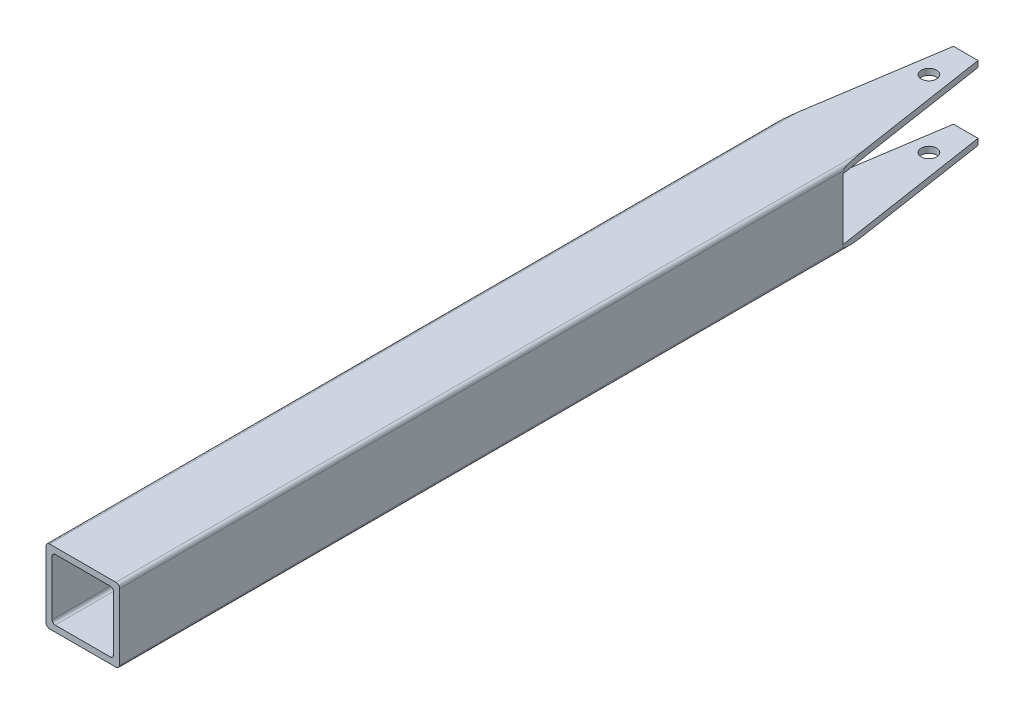
SolidWorks part; units mm, degrees
ref_plane "Front" through (0, 0, 0) normal (0, 0, 1) x (1, 0, 0)
ref_plane "Top" through (0, 0, 0) normal (0, 1, 0) x (1, 0, 0)
ref_plane "Right" through (0, 0, 0) normal (1, 0, 0) x (0, 0, -1)
sketch "Sketch1" plane through (0, 0, 0) normal (0, 0, 1) x (1, 0, 0)
  line L0 (-31.75, 0) -> (-38.1, 0) construction
  line L1 (34.29, -38.1) -> (-34.29, -38.1)
  line L2 (38.1, -34.29) -> (38.1, 34.29)
  line L3 (34.29, 38.1) -> (-34.29, 38.1)
  line L4 (-38.1, -34.29) -> (-38.1, 34.29)
  line L5 (38.1, -38.1) -> (-38.1, 38.1) construction
  line L6 (38.1, 38.1) -> (-38.1, -38.1) construction
  line L7 (28.575, 31.75) -> (-28.575, 31.75)
  line L8 (31.75, 28.575) -> (31.75, -28.575)
  line L9 (28.575, -31.75) -> (-28.575, -31.75)
  line L10 (-31.75, 28.575) -> (-31.75, -28.575)
  line L11 (31.75, 31.75) -> (-31.75, -31.75) construction
  line L12 (31.75, -31.75) -> (-31.75, 31.75) construction
  line L13 (0, -31.75) -> (0, -38.1) construction
  line L14 (31.75, -28.575) -> (31.75, -38.1) construction
  line L16 (31.75, -38.1) -> (38.1, -38.1) construction
  arc A0 (-28.575, -31.75) -> (-31.75, -28.575) centre (-28.575, -28.575) cw
  arc A1 (31.75, -28.575) -> (28.575, -31.75) centre (28.575, -28.575) cw
  arc A2 (28.575, 31.75) -> (31.75, 28.575) centre (28.575, 28.575) cw
  arc A3 (-28.575, 31.75) -> (-31.75, 28.575) centre (-28.575, 28.575) ccw
  arc A4 (34.29, -38.1) -> (38.1, -34.29) centre (34.29, -34.29) ccw
  arc A5 (38.1, 34.29) -> (34.29, 38.1) centre (34.29, 34.29) ccw
  arc A6 (-34.29, 38.1) -> (-38.1, 34.29) centre (-34.29, 34.29) ccw
  arc A7 (-34.29, -38.1) -> (-38.1, -34.29) centre (-34.29, -34.29) cw
  point P0 (0, 0)
  point P6 (0, 0)
  dimension "D2" = 3.175
  dimension "D3" = 3.81
sketch "Sketch2" plane through (0, 0, 0) normal (1, 0, 0) x (0, 0, -1)
  line L0 (-457.2, 0) -> (457.2, 0) construction
  dimension "Length" = 914.4
ref_plane "Plane1" through (38.1, 0, 0) normal (1, 0, 0) x (0, 0, -1)
sketch "Sketch5" plane through (38.1, 0, 0) normal (1, 0, 0) x (0, 0, -1)
  line L0 (-457.2, 38.1) -> (-457.2, -38.1) construction
  line L1 (457.2, 38.1) -> (457.2, -38.1) construction
sketch "Sketch4" plane through (0, 0, 0) normal (0, 0, 1) x (1, 0, 0)
  line L0 (38.1, -34.29) -> (38.1, 34.29) construction
  line L1 (34.29, 38.1) -> (-34.29, 38.1) construction
  line L2 (-38.1, -34.29) -> (-38.1, 34.29) construction
  line L3 (34.29, -38.1) -> (-34.29, -38.1) construction
  line L4 (31.75, 28.575) -> (31.75, -28.575) construction
  line L5 (28.575, -31.75) -> (-28.575, -31.75) construction
  line L6 (-31.75, 28.575) -> (-31.75, -28.575) construction
  line L7 (28.575, 31.75) -> (-28.575, 31.75) construction
  line L8 (38.1, -34.29) -> (38.1, 34.29)
  line L9 (34.29, 38.1) -> (-34.29, 38.1)
  line L10 (-38.1, -34.29) -> (-38.1, 34.29)
  line L11 (34.29, -38.1) -> (-34.29, -38.1)
  line L12 (31.75, 28.575) -> (31.75, -28.575)
  line L13 (28.575, -31.75) -> (-28.575, -31.75)
  line L14 (-31.75, 28.575) -> (-31.75, -28.575)
  line L15 (28.575, 31.75) -> (-28.575, 31.75)
  arc A0 (38.1, 34.29) -> (34.29, 38.1) centre (34.29, 34.29) ccw construction
  arc A1 (-34.29, 38.1) -> (-38.1, 34.29) centre (-34.29, 34.29) ccw construction
  arc A2 (-38.1, -34.29) -> (-34.29, -38.1) centre (-34.29, -34.29) ccw construction
  arc A3 (34.29, -38.1) -> (38.1, -34.29) centre (34.29, -34.29) ccw construction
  arc A4 (28.575, -31.75) -> (31.75, -28.575) centre (28.575, -28.575) ccw construction
  arc A5 (-31.75, -28.575) -> (-28.575, -31.75) centre (-28.575, -28.575) ccw construction
  arc A6 (-28.575, 31.75) -> (-31.75, 28.575) centre (-28.575, 28.575) ccw construction
  arc A7 (31.75, 28.575) -> (28.575, 31.75) centre (28.575, 28.575) ccw construction
  arc A8 (38.1, 34.29) -> (34.29, 38.1) centre (34.29, 34.29) ccw
  arc A9 (-34.29, 38.1) -> (-38.1, 34.29) centre (-34.29, 34.29) ccw
  arc A10 (-38.1, -34.29) -> (-34.29, -38.1) centre (-34.29, -34.29) ccw
  arc A11 (34.29, -38.1) -> (38.1, -34.29) centre (34.29, -34.29) ccw
  arc A12 (28.575, -31.75) -> (31.75, -28.575) centre (28.575, -28.575) ccw
  arc A13 (-31.75, -28.575) -> (-28.575, -31.75) centre (-28.575, -28.575) ccw
  arc A14 (-28.575, 31.75) -> (-31.75, 28.575) centre (-28.575, 28.575) ccw
  arc A15 (31.75, 28.575) -> (28.575, 31.75) centre (28.575, 28.575) ccw
extrude "Boss-Extrude1" add sketch "Sketch4" along normal up to vertex (457.2 mm away) and the other way up to vertex (457.2 mm away) up to point (0, 0, 457.2) other way up to point (0, 0, -457.2)
sketch "Sketch6" plane through (-38.1, 0, 0) normal (-1, 0, 0) x (0, 0, 1)
  line L0 (-457.2, -31.75) -> (-371.4675, -31.75) construction
  line L1 (-457.2, 31.75) -> (-292.1, 31.75)
  line L2 (-457.2, 31.75) -> (-457.2, -31.75)
  line L3 (-457.2, -31.75) -> (-292.1, -31.75)
  line L4 (-292.1, 31.75) -> (-292.1, -31.75)
  point P5 (-457.2, -31.75)
  dimension "D1" = 165.1
extrude "side cut" cut sketch "Sketch6" against normal through all
sketch "Sketch7" plane through (0, -38.1, 0) normal (0, -1, 0) x (1, 0, 0)
  line L0 (0, -457.2) -> (0, -341.7828) construction
  line L1 (-34.29, -457.2) -> (34.29, -457.2) construction
  line L2 (-38.1, -292.1) -> (-38.1, -457.2)
  line L3 (-38.1, -457.2) -> (-12.7, -457.2)
  line L4 (-12.7, -457.2) -> (-38.1, -292.1)
  line L5 (12.7, -457.2) -> (38.1, -292.1)
  line L6 (38.1, -457.2) -> (12.7, -457.2)
  line L7 (38.1, -292.1) -> (38.1, -457.2)
  dimension "D1" = 25.4
extrude "triangle cut" cut sketch "Sketch7" against normal through all
sketch "Sketch8" plane through (0, 38.1, 0) normal (0, 1, 0) x (1, 0, 0)
  line L0 (0, 457.2) -> (0, 353.4841) construction
  line L1 (12.7, 457.2) -> (-12.7, 457.2) construction
  circle A0 centre (0, 419.1) radius 7.9375
  dimension "D1" = 15.875
  dimension "D2" = 38.1
extrude "Cut-Extrude4" cut sketch "Sketch8" against normal through all
sketch "Sketch9" plane through (38.1, 0, 0) normal (1, 0, 0) x (0, 0, -1)
  line L0 (411.1625, 34.925) -> (427.0375, 34.925) construction
  line L1 (411.1625, 38.1) -> (411.1625, 31.75) construction
  line L2 (427.0375, 31.75) -> (427.0375, 38.1) construction
  line L3 (411.1625, -34.925) -> (427.0375, -34.925) construction
  line L4 (411.1625, -31.75) -> (411.1625, -38.1) construction
  line L5 (427.0375, -38.1) -> (427.0375, -31.75) construction
  line L6 (419.1, -34.925) -> (419.1, 34.925) construction
  line L7 (419.1, 0) -> (-271.78, 0)
  point P18 (-271.78, 0)
  dimension "D1" = 690.88
equation "\"D3@Sketch1\"=\"Outside Width@Sketch1\"*.05"
equation "\"D2@Sketch1\"=\"D1@Sketch1\"*.05"
equation "\"mountingPointDistance\"=27.2"
equation "\"D1@Sketch9\"=\"mountingPointDistance\""
